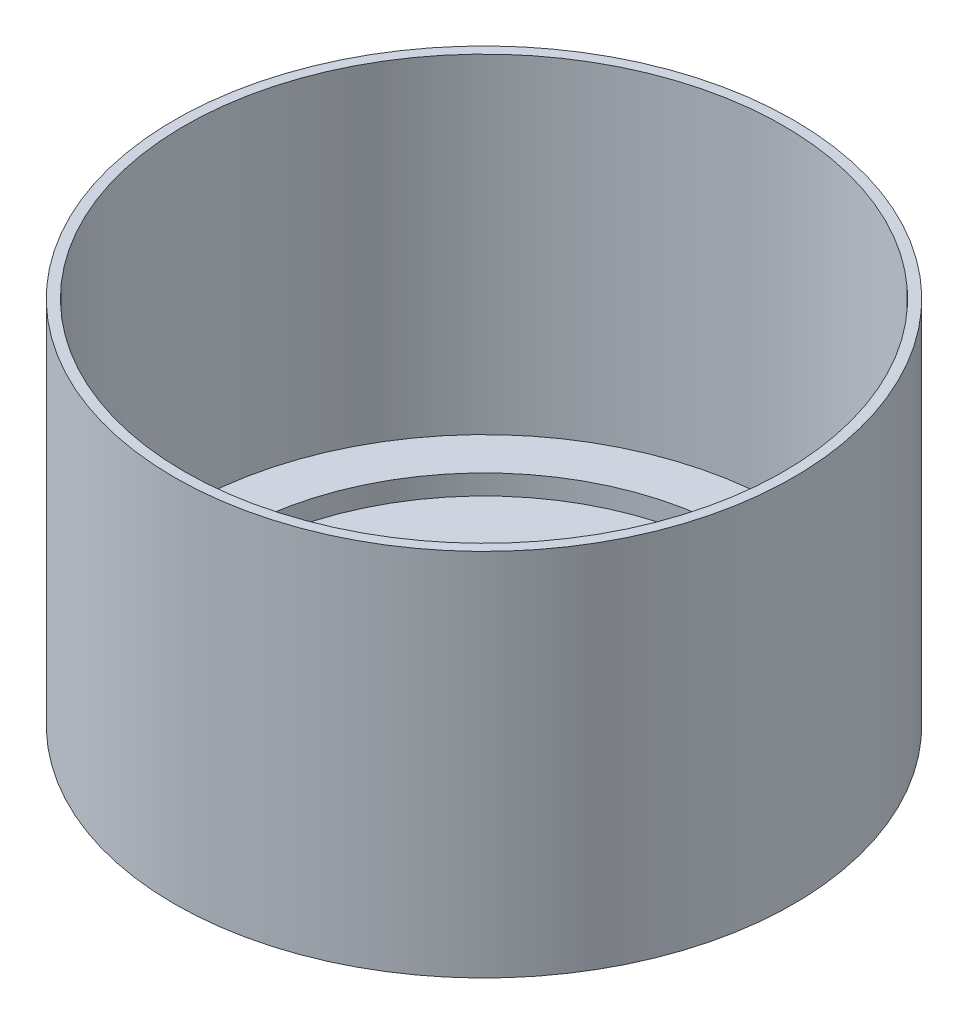
SolidWorks part; units mm, degrees
ref_plane "Alzado" through (0, 0, 0) normal (0, 0, 1) x (1, 0, 0)
ref_plane "Planta" through (0, 0, 0) normal (0, 1, 0) x (1, 0, 0)
ref_plane "Vista lateral" through (0, 0, 0) normal (1, 0, 0) x (0, 0, -1)
sketch "Sketch1" plane through (0, 0, 0) normal (0, 1, 0) x (1, 0, 0)
  circle A2 centre (0, 0) radius 30
  circle A3 centre (0, 0) radius 31
  dimension "D1" = 60
  dimension "D2" = 62
extrude "Boss-Extrude1" add sketch "Sketch1" along normal blind 37
sketch "Sketch2" plane through (0, 0, 0) normal (0, 1, 0) x (1, 0, 0)
  circle A0 centre (0, 0) radius 31
extrude "Boss-Extrude2" add sketch "Sketch2" along normal blind 2
sketch "Sketch5" plane through (0, 2, 0) normal (0, 1, 0) x (1, 0, 0)
  circle A0 centre (0, 0) radius 30
  circle A1 centre (0, 0) radius 25.3
  dimension "5.7" = 4.7
extrude "Boss-Extrude4" add sketch "Sketch5" along normal blind 2
sketch "Sketch6" plane through (0, 2, 0) normal (0, 1, 0) x (1, 0, 0)
  circle A0 centre (0, 0) radius 4
  dimension "D1" = 8
extrude "Cut-Extrude1" cut sketch "Sketch6" against normal blind 2
